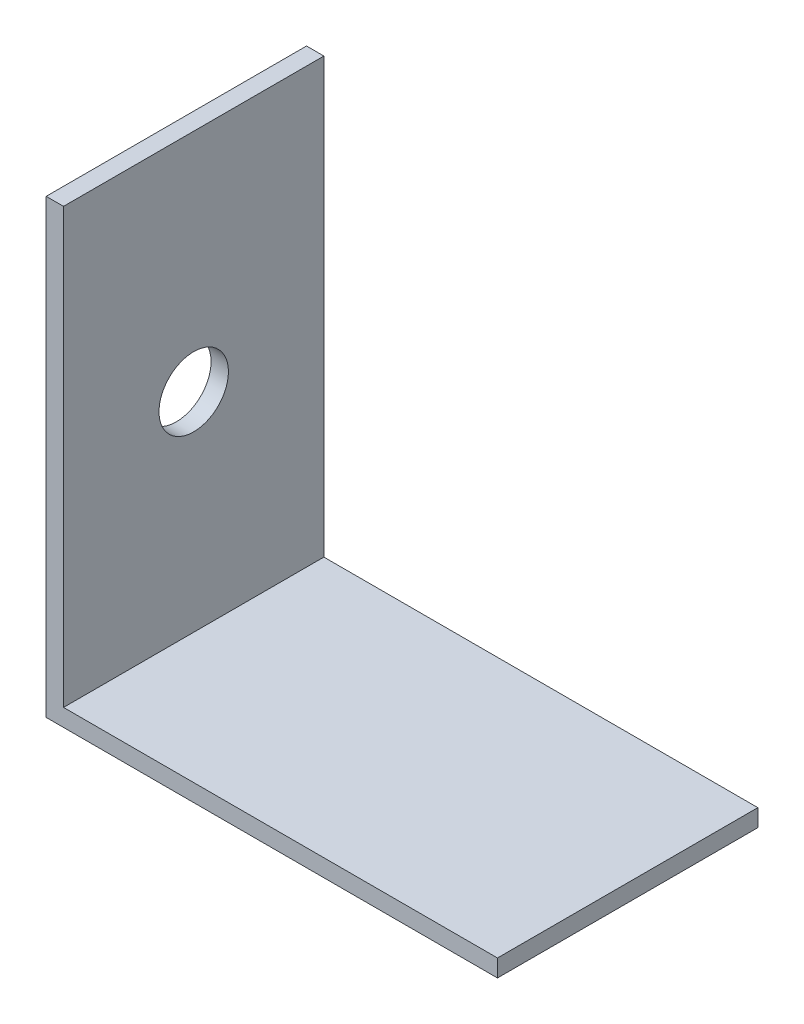
SolidWorks part; units mm, degrees
ref_plane "Plano frontal" through (0, 0, 0) normal (0, 0, 1) x (1, 0, 0)
ref_plane "Plano superior" through (0, 0, 0) normal (0, 1, 0) x (1, 0, 0)
ref_plane "Plano direito" through (0, 0, 0) normal (1, 0, 0) x (0, 0, -1)
sketch "Esboço1" plane through (0, 0, 0) normal (0, 0, 1) x (1, 0, 0)
  line L0 (0, 0) -> (25, 0)
  line L1 (0, 0) -> (0, 25)
  line L2 (-1, -1) -> (-1, 25)
  line L3 (-1, -1) -> (25, -1)
  line L4 (0, 25) -> (-1, 25)
  line L5 (25, 0) -> (25, -1)
  dimension "D1" = 25
  dimension "D2" = 1
extrude "Ressalto-extrusão1" add sketch "Esboço1" along normal blind 15
sketch "Esboço2" plane through (0, 0, 0) normal (1, 0, 0) x (0, 0, -1)
  line L0 (0, 12) -> (-15, 12) construction
  line L1 (0, 25) -> (0, -1) construction
  line L2 (-15, 25) -> (-15, -1) construction
  circle A0 centre (-7.5, 12) radius 2
extrude "Corte-extrusão1" cut sketch "Esboço2" against normal blind 15
